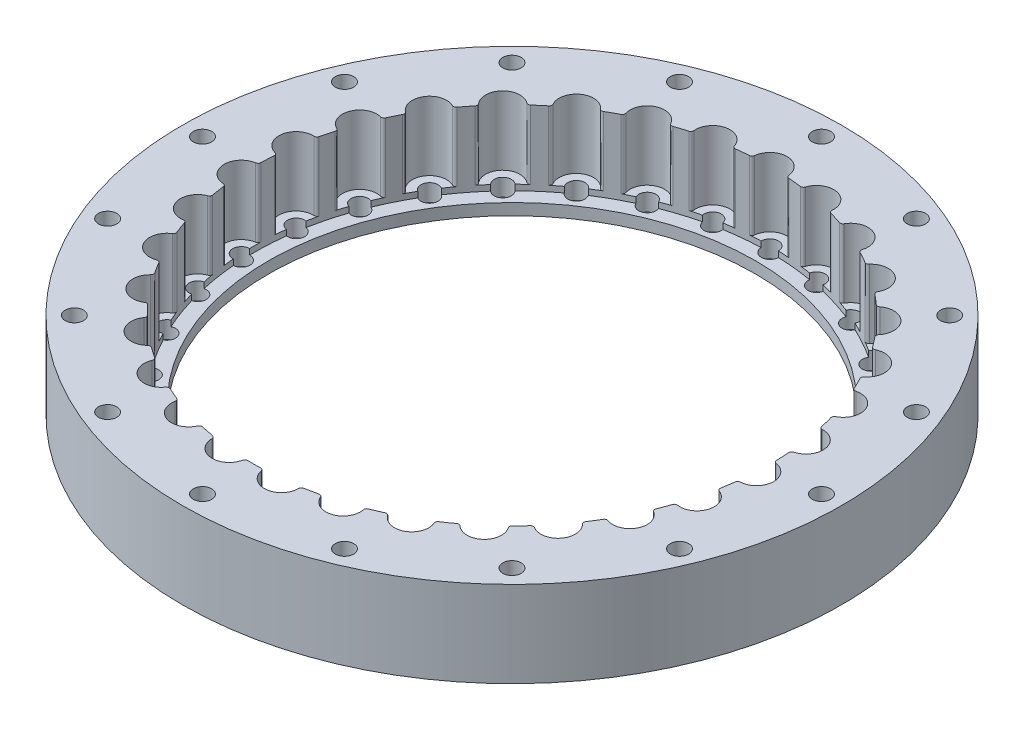
SolidWorks part; units mm, degrees
ref_plane "Front Plane" through (0, 0, 0) normal (0, 0, 1) x (1, 0, 0)
ref_plane "Top Plane" through (0, 0, 0) normal (0, 1, 0) x (1, 0, 0)
ref_plane "Right Plane" through (0, 0, 0) normal (1, 0, 0) x (0, 0, -1)
sketch "Sketch1" plane through (0, 0, 0) normal (0, 1, 0) x (1, 0, 0)
  line L0 (15.8389, 51.6249) -> (0, 0) construction
  line L1 (0, 0) -> (-4.5526, -44.7691) construction
  circle A0 centre (0, 0) radius 45
  circle A12 centre (0, 0) radius 57.5
  circle A13 centre (0, 0) radius 54 construction
  point P27 (0, 0)
  point P54 (0, 0)
  dimension "D1" = 90
  dimension "D4" = 115
  dimension "D5" = 108
  dimension "D8" = 11.25
extrude "Boss-Extrude1" add sketch "Sketch1" along normal blind 12 contours A12 region at (-55.8737, 0, 0)
sketch "Sketch2" plane through (0, 0, 0) normal (0, -1, 0) x (1, 0, 0)
  circle A0 centre (0, 0) radius 57.5
  circle A1 centre (0, 0) radius 45
extrude "Boss-Extrude2" add sketch "Sketch2" along normal blind 1
sketch "Sketch3" plane through (0, -1, 0) normal (0, -1, 0) x (1, 0, 0)
  circle A0 centre (0, 0) radius 57.5
  circle A1 centre (0, 0) radius 42.5
  dimension "D1" = 85
extrude "Boss-Extrude3" add sketch "Sketch3" along normal blind 2
sketch "Sketch5" plane through (0, 12, 0) normal (0, 1, 0) x (1, 0, 0)
  circle A0 centre (0, 45) radius 3
  circle A1 centre (0, 0) radius 45 construction
  circle A2 centre (0, 0) radius 45 construction
  dimension "D1" = 6
extrude "Cut-Extrude2" cut sketch "Sketch5" against normal blind 12
fillet "Fillet4" radius 0.5 2 edges at (2.9983, 6, -44.9) (-2.9983, 6, -44.9)
sketch "Sketch7" plane through (0, 0, 0) normal (0, 1, 0) x (1, 0, 0)
  circle A0 centre (0, 45) radius 1.5
  arc A1 (3.4425, 44.8681) -> (-3.4425, 44.8681) centre (0, 0) ccw construction
  dimension "D1" = 3
extrude "Cut-Extrude3" cut sketch "Sketch7" against normal blind 10
pattern_circular "CirPattern3" count 31 over 360 about axis through (0, -3, 0) along (0, 1, 0) of "Cut-Extrude2", "Fillet4", "Cut-Extrude3"
sketch "Sketch4" plane through (0, 12, 0) normal (0, 1, 0) x (1, 0, 0)
  circle A0 centre (0, 0) radius 54 construction
  circle A1 centre (0, 54) radius 1.6
  circle A2 centre (20.6649, 49.8895) radius 1.6
  circle A3 centre (38.1838, 38.1838) radius 1.6
  circle A4 centre (49.8895, 20.6649) radius 1.6
  circle A5 centre (54, 0) radius 1.6
  circle A6 centre (49.8895, -20.6649) radius 1.6
  circle A7 centre (38.1838, -38.1838) radius 1.6
  circle A8 centre (20.6649, -49.8895) radius 1.6
  circle A9 centre (0, -54) radius 1.6
  circle A10 centre (-20.6649, -49.8895) radius 1.6
  circle A11 centre (-38.1838, -38.1838) radius 1.6
  circle A12 centre (-49.8895, -20.6649) radius 1.6
  circle A13 centre (-54, 0) radius 1.6
  circle A14 centre (-49.8895, 20.6649) radius 1.6
  circle A15 centre (-38.1838, 38.1838) radius 1.6
  circle A16 centre (-20.6649, 49.8895) radius 1.6
  circle A17 centre (0, 0) radius 45 construction
  point P38 (0, 0)
  point P102 (0, 0)
  dimension "D1" = 108
  dimension "D2" = 3.2
extrude "Cut-Extrude1" cut sketch "Sketch4" against normal blind 51
